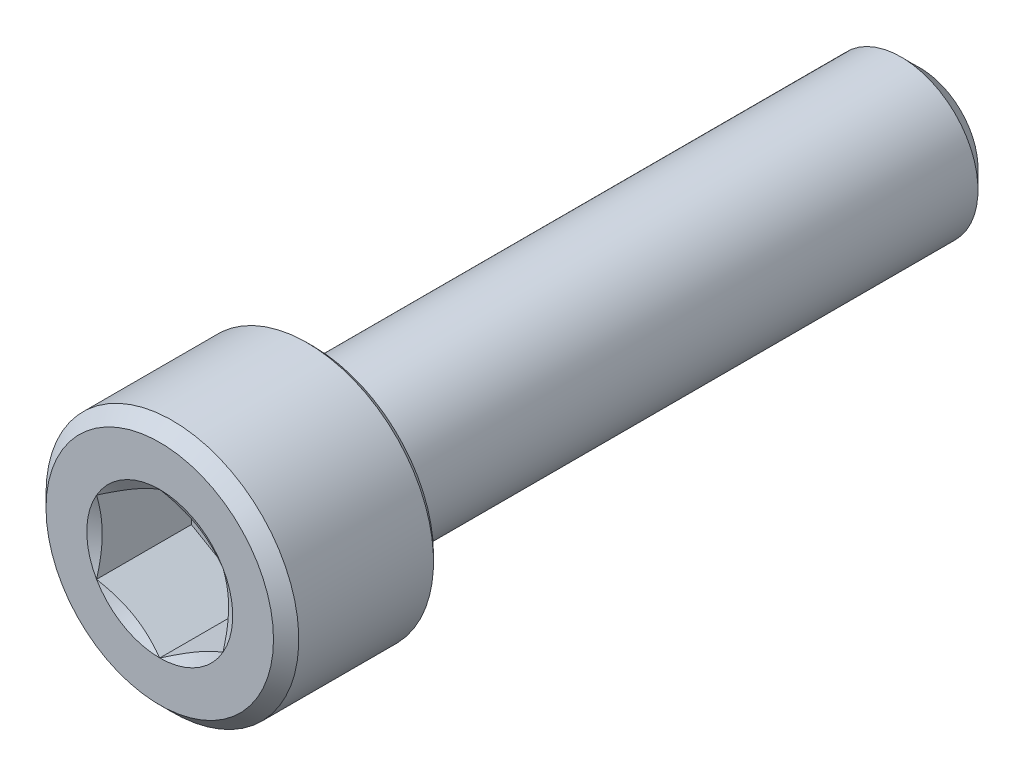
SolidWorks part; units mm, degrees
ref_plane "Front Plane" through (0, 0, 0) normal (0, 0, 1) x (1, 0, 0)
ref_plane "Top Plane" through (0, 0, 0) normal (0, 1, 0) x (1, 0, 0)
ref_plane "Right Plane" through (0, 0, 0) normal (1, 0, 0) x (0, 0, -1)
sketch "Sketch1" plane through (0, 0, 0) normal (1, 0, 0) x (0, 0, -1)
  line L0 (11.938, 0) -> (-11.938, 0) construction
  line L1 (-11.938, 0) -> (-11.938, 3.9687) construction
  line L2 (-7.112, 2.413) -> (-7.112, 0) construction
  line L3 (11.1443, 0) -> (11.1443, 0.7938) construction
  line L4 (-7.112, 0) -> (-7.112, -2.413) construction
  point P6 (-11.938, 1.9844)
  point P9 (-11.938, -1.9844)
  point P10 (-7.112, 0)
  point P13 (9.1599, -2.413)
  dimension "D1" = 0.7937
  dimension "D2" = 2.7781
sketch "Sketch2" plane through (0, 0, 0) normal (1, 0, 0) x (0, 0, -1)
  line L0 (11.938, 1.8177) -> (11.3427, 2.413)
  line L1 (-11.938, 3.9687) -> (-7.112, 3.9687)
  line L2 (-11.938, 3.9687) -> (-11.938, 0)
  line L4 (-7.112, 3.9687) -> (-7.112, 2.413)
  line L5 (-7.112, 2.413) -> (11.3427, 2.413)
  line L8 (11.938, 1.8177) -> (11.938, 0)
  line L9 (11.938, 0) -> (-11.938, 0) construction
  line L10 (11.938, 0) -> (-11.938, 0)
  dimension "D1" = 135
  dimension "D2" = 0.5953
revolve "Revolve1" add sketch "Sketch2" angle 360 about L10
sketch "Sketch4" plane through (0, 0, 11.938) normal (0, 0, 1) x (1, 0, 0)
  line L1 (0, 2.2914) -> (-1.9844, 1.1457)
  line L2 (-1.9844, 1.1457) -> (-1.9844, -1.1457)
  line L3 (-1.9844, -1.1457) -> (0, -2.2914)
  line L4 (0, -2.2914) -> (1.9844, -1.1457)
  line L5 (1.9844, -1.1457) -> (1.9844, 1.1457)
  line L6 (1.9844, 1.1457) -> (0, 2.2914)
  circle A0 centre (0, 0) radius 1.9844 construction
  circle A1 centre (0, 0) radius 3.9687 construction
  circle A2 centre (0, 0) radius 3.9687 construction
  dimension "D1" = 3.9688
extrude "Cut-Extrude1" cut sketch "Sketch4" against normal blind 2.9766
sketch "Sketch5" plane through (0, 0, 11.938) normal (0, 0, 1) x (1, 0, 0)
  circle A0 centre (0, 0) radius 2.2914
extrude "Cut-Extrude2" cut sketch "Sketch5" against normal blind 10 draft 60
chamfer "Chamfer1" distance 0.3969 angle 45 1 edges at (-3.9687, 0, 11.938)
chamfer "Chamfer2" distance 0.1984 angle 45 1 edges at (-3.9687, 0, 7.112)
sketch "Sketch3" [suppressed] plane through (0, 0, -8.763) normal (0, 0, -1) x (-1, 0, 0)
  circle A0 centre (0, 0) radius 2.413 construction
  circle A1 centre (0, 0) radius 2.413
ref_axis "Center Axis1" through (0, 0, -5.7312) along (0, 0, 1)
ref_plane "Contact Plane1" through (0, 0, -11.938) normal (0, 0, 1) x (1, 0, 0)
ref_plane "Contact Plane2" through (0, 0, 7.112) normal (0, 0, 1) x (1, 0, 0)
split "Split1" [suppressed] bodies to split 106
curve "Helix/Spiral1" [suppressed]
sketch "Sketch7" [suppressed] plane through (0, 0, 0) normal (1, 0, 0) x (0, 0, -1)
  line L0 (8.7134, 2.4989) -> (9.1103, 1.8115) construction
  line L1 (9.1103, 1.8115) -> (9.5071, 2.4989) construction
  line L2 (9.5071, 2.4989) -> (8.7134, 2.4989) construction
  line L3 (8.763, 2.413) -> (9.4575, 2.413)
  line L4 (9.1103, 2.4989) -> (9.1103, 2.413) construction
  line L5 (9.1103, 2.413) -> (9.1103, 1.8974) construction
  line L6 (9.1103, 1.8974) -> (9.1103, 1.8115) construction
  line L7 (9.0607, 1.8974) -> (9.1599, 1.8974)
  line L8 (8.7382, 2.456) -> (9.4823, 2.456) construction
  line L9 (9.1599, 1.8974) -> (9.4575, 2.413)
  line L10 (9.0607, 1.8974) -> (8.763, 2.413)
  point P0 (9.1103, 2.456)
  dimension "D1" = 0.7937
  dimension "D2" = 0.0992
sweep "Cut-Sweep1" [suppressed] cut profiles "Sketch7" path "Helix/Spiral1"
sketch "Sketch11" [suppressed] plane through (0, 0, 3.937) normal (0, 0, -1) x (-1, 0, 0)
  circle A0 centre (0, 0) radius 2.413
extrude "Boss-Extrude4" [suppressed] add sketch "Sketch11" along normal through all draft 45
sketch "Sketch9" [suppressed] plane through (0, 0, 3.937) normal (0, 0, -1) x (-1, 0, 0)
  line L0 (0, 0) -> (0, 3.9687) construction
  line L1 (0, 3.7703) -> (-0.416, 4.1672)
  line L2 (-0.416, 4.1672) -> (0.416, 4.1672)
  line L3 (0.416, 4.1672) -> (0, 3.7703)
  line L4 (-0.208, 3.9688) -> (0, 0) construction
  line L5 (0, 0) -> (0.208, 3.9688) construction
  circle A0 centre (0, 0) radius 3.9687 construction
  circle A1 centre (0, 0) radius 3.7703 construction
  dimension "D1" = 0.3969
  dimension "D2" = 6
extrude "Cut-Extrude3" [suppressed] cut sketch "Sketch9" against normal up to next
pattern_circular "CirPattern1" [suppressed] count 60 over 360 of bodies 112
equation "\"D1@Sketch1\"=\"Pitch@Sketch1\""
equation "\"D2@Sketch2\"=\"D1@Sketch1\"*.75"
equation "\"D4@Helix/Spiral1\"=\"Pitch@Sketch1\""
equation "\"D3@Helix/Spiral1\"=\"Length@Sketch1\"+\"Pitch@Sketch1\""
equation "\"D1@Sketch4\" = \"Drive Size@Sketch1\""
equation "\"D1@Cut-Extrude1\"=\"D1@Sketch4\"*.75"
equation "\"D19\"= \"D1@Sketch4\" * .75"
equation "\"D1@Chamfer1\" = \"Head Diameter@Sketch1\" * .05"
equation "\"D1@Chamfer2\"=\"D1@Chamfer1\"/2"
equation "\"D2@Sketch7\"=\"D1@Sketch7\"/8"
equation "\"D1@Sketch7\"=\"D4@Helix/Spiral1\""
equation "\"D2@Sketch1\"=\"Pitch@Sketch1\"*3.5"
equation "\"D1@Sketch9\"=\"D1@Chamfer1\""
equation "\"D1@CirPattern1\"=\"D3@CirPattern1\"/\"D2@Sketch9\""
